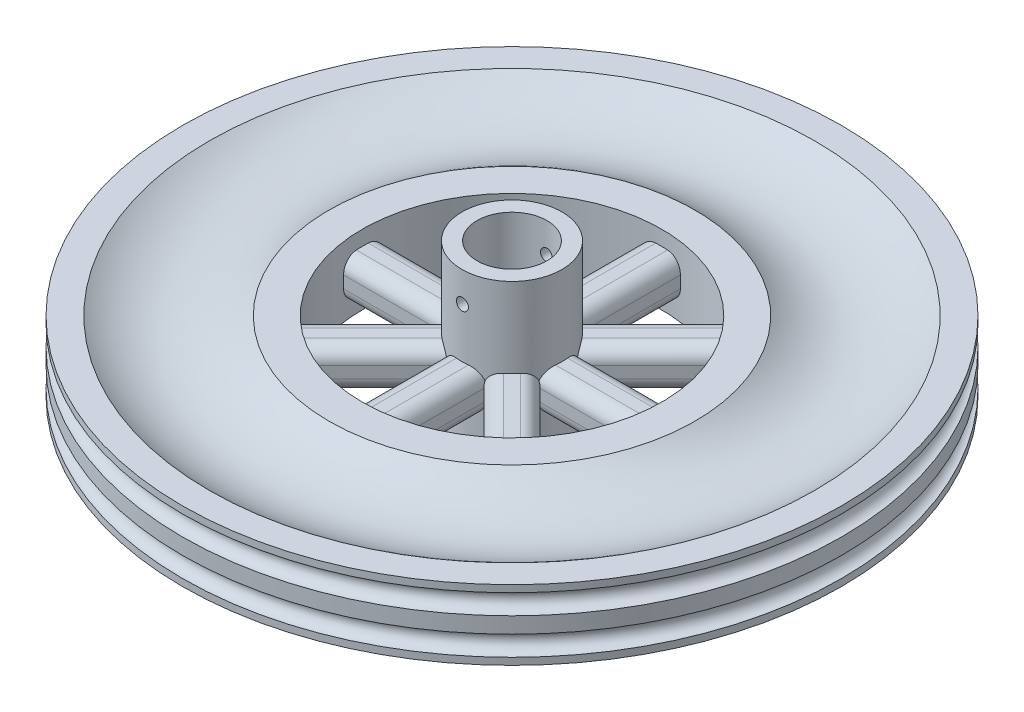
SolidWorks part; units mm, degrees
material "1023 Carbon Steel Sheet (SS)"
ref_plane "Front Plane" through (0, 0, 0) normal (0, 0, 1) x (1, 0, 0)
ref_plane "Top Plane" through (0, 0, 0) normal (0, 1, 0) x (1, 0, 0)
ref_plane "Right Plane" through (0, 0, 0) normal (1, 0, 0) x (0, 0, -1)
sketch "Sketch1" plane through (0, 0, 0) normal (0, 0, 1) x (1, 0, 0)
  line L0 (-298.3246, 0) -> (272.9843, 0) construction
  line L1 (0, 170.7592) -> (0, -173.0628) construction
  line L2 (0, 50) -> (-25, 50)
  line L3 (-25, 50) -> (-25, -50)
  line L4 (-25, -50) -> (0, -50)
  line L5 (0, -50) -> (0, 50)
  dimension "D1" = 100
  dimension "D2" = 50
  dimension "D3" = 50
revolve "Revolve1" add sketch "Sketch1" angle 360 about L1
sketch "Sketch4" plane through (0, 0, 0) normal (0, 0, 1) x (1, 0, 0)
  line L0 (0, 50) -> (15, 50)
  line L1 (25, 50) -> (-25, 50) construction
  line L2 (15, 50) -> (8, 42)
  line L3 (8, 42) -> (8, -50)
  line L4 (-25, -50) -> (25, -50) construction
  line L5 (8, -50) -> (0, -50)
  line L6 (0, -50) -> (0, 50)
  line L7 (0, 71.2188) -> (0, -76.1792) construction
  dimension "D1" = 30
  dimension "D2" = 8
  dimension "D3" = 16
sketch "Sketch5" plane through (0, 0, 0) normal (0, 0, 1) x (1, 0, 0)
  line L0 (-333.7999, 0) -> (79.0837, 0) construction
  line L1 (-75, 17.5) -> (-75, -17.5)
  line L2 (-75, -17.5) -> (-91.6087, -17.5)
  line L3 (-165, -17.5) -> (-165, -14)
  line L4 (-165, 17.5) -> (-151.6087, 17.5)
  line L5 (-96.2392, 57.5) -> (-290.2164, 57.5) construction
  line L6 (-120, 108.9208) -> (-120, -94.878) construction
  line L7 (0, 93.5184) -> (0, -105.9352) construction
  line L8 (-91.6087, 17.5) -> (-75, 17.5)
  line L9 (-91.6087, -17.5) -> (-75, -17.5)
  line L10 (-165, -17.5) -> (-151.6087, -17.5)
  line L11 (-151.6087, -17.5) -> (-165, -17.5)
  line L12 (-165, 14) -> (-165, 17.5)
  line L13 (-165, -4) -> (-165, 4)
  arc A0 (-151.6087, 17.5) -> (-91.6087, 17.5) centre (-121.6087, 57.5) ccw
  arc A1 (-151.6087, -17.5) -> (-91.6087, -17.5) centre (-121.6087, -57.5) cw
  arc A2 (-165, 4) -> (-165, 14) centre (-165, 9) ccw
  arc A3 (-165, -14) -> (-165, -4) centre (-165, -9) ccw
  dimension "D4" = 100
  dimension "D5" = 10
  dimension "D6" = 10
  dimension "D1" = 40
  dimension "D2" = 35
  dimension "D3" = 150
  dimension "D7" = 8
  dimension "D8" = 13.3913
  dimension "D9" = 45
revolve "Revolve2" add sketch "Sketch5" angle 360 about L7 region at (-117.9224, 0, 0)
sketch "Sketch6" plane through (0, 0, 0) normal (1, 0, 0) x (0, 0, -1)
  line L1 (3, 10) -> (-3, 10)
  line L2 (10, 3) -> (10, -3)
  line L3 (3, -10) -> (-3, -10)
  line L4 (-10, 3) -> (-10, -3)
  line L5 (10, 10) -> (-10, -10) construction
  line L6 (10, -10) -> (-10, 10) construction
  arc A0 (-3, -10) -> (-10, -3) centre (-3, -3) cw
  arc A1 (10, -3) -> (3, -10) centre (3, -3) cw
  arc A2 (10, 3) -> (3, 10) centre (3, 3) ccw
  arc A3 (-10, 3) -> (-3, 10) centre (-3, 3) cw
  point P0 (0, 0)
  dimension "D3" = 7
  dimension "D1" = 20
  dimension "D2" = 20
extrude "Boss-Extrude1" add sketch "Sketch6" along normal up to surface (74.94 mm away) up to face at (0, -17.5, 75)
ref_axis "Axis1" through (0, -59.2906, 0) along (0, 1, 0)
pattern_circular "CirPattern1" count 8 over 360 of "Boss-Extrude1"
sketch "Sketch7" plane through (0, 50, 0) normal (0, 1, 0) x (1, 0, 0)
  circle A0 centre (0, 0) radius 17.5
  dimension "D1" = 35
extrude "Cut-Extrude1" cut sketch "Sketch7" against normal blind 92
sketch "Sketch8" plane through (0, 0, 0) normal (0, 0, 1) x (1, 0, 0)
  line L0 (25, 50) -> (-25, 50) construction
  circle A0 centre (0, 35) radius 3
  dimension "D1" = 6
  dimension "D2" = 15
extrude "Cut-Extrude2" cut sketch "Sketch8" against normal mid plane 50
fillet "Fillet1" radius 2 1 edges at (0, -50, 25)
